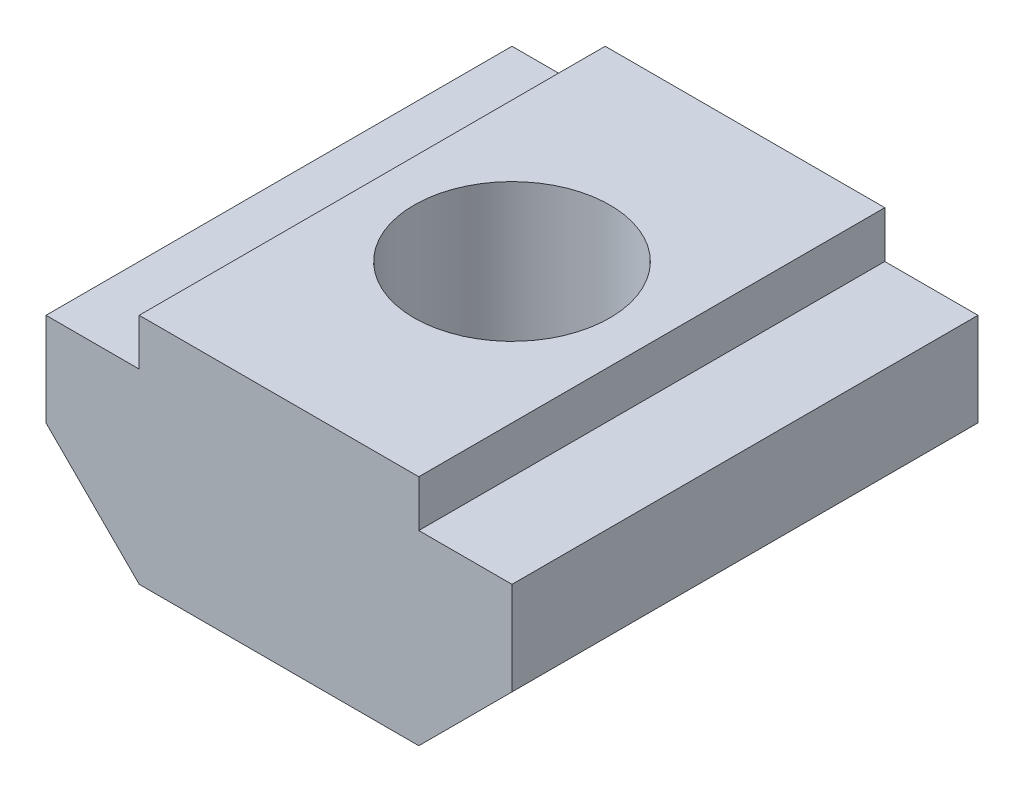
SolidWorks part; units mm, degrees
material "Aluminum 6105-T5"
ref_plane "Front Plane" through (0, 0, 0) normal (0, 0, 1) x (1, 0, 0)
ref_plane "Top Plane" through (0, 0, 0) normal (0, 1, 0) x (1, 0, 0)
ref_plane "Right Plane" through (0, 0, 0) normal (1, 0, 0) x (0, 0, -1)
sketch "Sketch1" plane through (0, 0, 0) normal (0, 0, 1) x (1, 0, 0)
  line L0 (-5, -0.5) -> (-3, -2.5)
  line L1 (-3, -2.5) -> (3, -2.5)
  line L2 (-3, -2.5) -> (-3, 2.5)
  line L3 (-3, 2.5) -> (3, 2.5)
  line L4 (3, -2.5) -> (3, 2.5)
  line L5 (-3, -2.5) -> (3, 2.5) construction
  line L6 (-3, 2.5) -> (3, -2.5) construction
  line L7 (-5, -2.5) -> (5, -2.5)
  line L8 (-5, -2.5) -> (-5, 1.5)
  line L9 (-5, 1.5) -> (5, 1.5)
  line L10 (5, -2.5) -> (5, 1.5)
  line L11 (5, -0.5) -> (3, -2.5)
  line L12 (-5, -0.5) -> (5, -0.5) construction
  line L13 (0, -0.5) -> (0, 0) construction
  point P0 (0, 0)
  dimension "D1" = 6
  dimension "D2" = 5
  dimension "D3" = 10
  dimension "D4" = 4
  dimension "D5" = 6
  dimension "D6" = 45
extrude "Boss-Extrude1" add sketch "Sketch1" along normal mid plane 10 contours L9 L8 L0 L7 L2 | L9 L2 L1 L4 | L2 L9 L4 L3 | L11 L10 L9 L4 L7 region at (-3.8889, -0.0556, 0) region at (0, -0.5, 0) region at (3.8889, -0.0556, 0) region at (0, 2, 0)
sketch "Sketch2" plane through (0, 2.5, 0) normal (0, 1, 0) x (1, 0, 0)
  circle A0 centre (0, 0) radius 2.1
  dimension "D1" = 4.2
extrude "Cut-Extrude1" cut sketch "Sketch2" against normal through all
